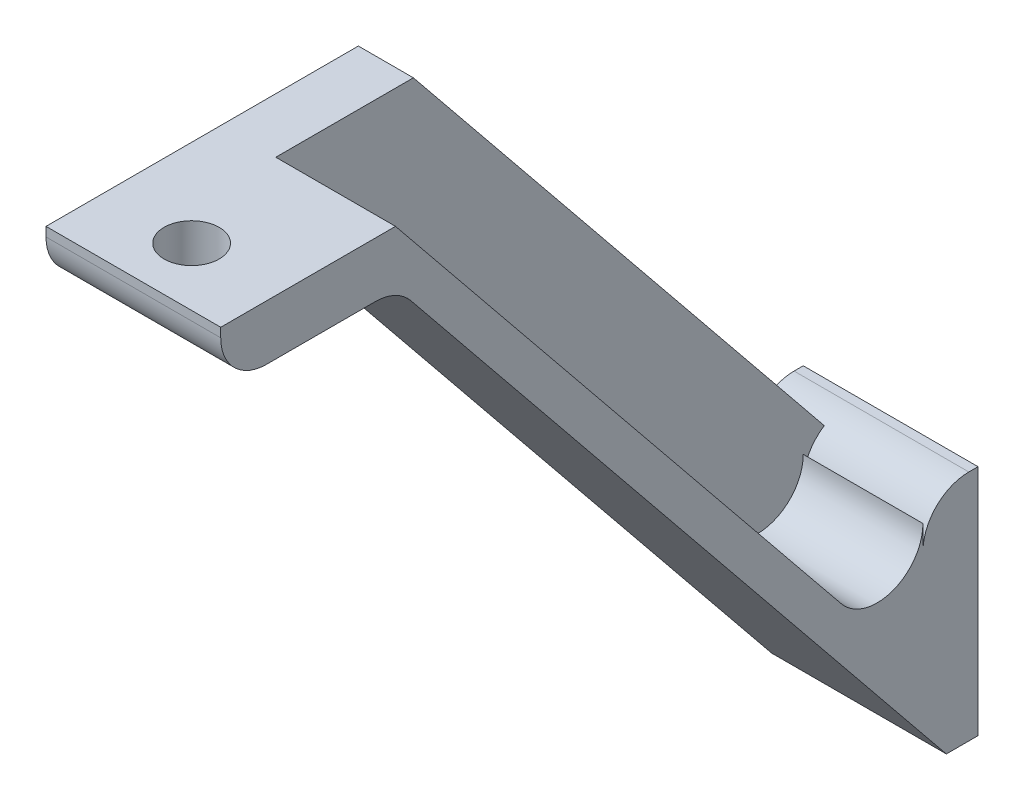
SolidWorks part; units mm, degrees
ref_plane "Front Plane" through (0, 0, 0) normal (0, 0, 1) x (1, 0, 0)
ref_plane "Top Plane" through (0, 0, 0) normal (0, 1, 0) x (1, 0, 0)
ref_plane "Right Plane" through (0, 0, 0) normal (1, 0, 0) x (0, 0, -1)
sketch "Sketch1" plane through (0, 0, 0) normal (1, 0, 0) x (0, 0, -1)
  line L0 (-17.31, 31.3863) -> (31.3064, -28.5635)
  line L1 (-36.36, 31.3863) -> (-17.31, 31.3863)
  line L2 (-36.36, 31.3863) -> (-36.36, 30.3863)
  line L3 (42.7403, -48.4513) -> (46.19, -48.4513)
  line L4 (46.19, -23.0513) -> (46.19, -48.4513)
  line L5 (-36.36, 31.3863) -> (-17.31, 31.3863)
  line L6 (-36.36, 31.3863) -> (-36.36, 25.3863)
  line L7 (-31.36, 25.3863) -> (-19.5212, 25.3863)
  line L9 (46.19, -48.4513) -> (42.7403, -48.4513)
  line L10 (46.19, -48.4513) -> (46.19, -23.0513)
  line L11 (46.19, -23.0513) -> (45.19, -23.0513)
  line L12 (40.19, -25.4142) -> (40.19, -28.0513)
  line L13 (42.7403, -48.4513) -> (-15.6376, 23.5357)
  arc A0 (45.19, -23.0513) -> (40.19, -28.0513) centre (45.19, -28.0513) ccw
  arc A1 (-36.36, 30.3863) -> (-31.36, 25.3863) centre (-31.36, 30.3863) ccw
  arc A2 (31.3064, -28.5635) -> (40.19, -25.4142) centre (35.19, -25.4142) ccw
  arc A3 (-19.5212, 25.3863) -> (-15.6376, 23.5357) centre (-19.5212, 20.3863) cw
  dimension "D1" = 5
  dimension "D2" = 63.5
  dimension "D3" = 180
  dimension "D4" = 25.4
  dimension "D5" = 6
  dimension "D6" = 6
extrude "Boss-Extrude2" add sketch "Sketch1" along normal blind 19.05 contours L7 A3 L13 L3 L4 L11 A0 L12 A2 L0 L1 L2 A1 region at (0, -8.9989, -13.7759)
sketch "Sketch3" plane through (0, 31.3863, 0) normal (0, 1, 0) x (1, 0, 0)
  line L0 (19.05, 46.19) -> (0, 46.19) construction
  circle A0 centre (9.525, -30.01) radius 3
  dimension "D1" = 76.2
  dimension "D2" = 6
extrude "Cut-Extrude1" cut sketch "Sketch3" against normal blind 19.05
sketch "Sketch4" plane through (0, 3.9836, -4.9123) normal (0, 0.6299, -0.7767) x (-1, 0, 0)
  line L1 (0, 35.2809) -> (-6, 35.2809)
  line L2 (0, 35.2809) -> (0, -53.1067)
  line L3 (0, -53.1067) -> (-6, -53.1067)
  line L4 (-6, 35.2809) -> (-6, -53.1067)
  dimension "D1" = 6
extrude "Boss-Extrude3" add sketch "Sketch4" along direction (0, 0, -1) on the side of the normal blind 15
sketch "Sketch5" plane through (19.05, 0, 0) normal (1, 0, 0) x (0, 0, -1)
  line L0 (46.19, -23.0513) -> (46.19, -48.4513) construction
  line L1 (46.19, -25.9204) -> (57.4552, -25.9204)
  line L2 (46.19, -25.9204) -> (46.19, -39.5883)
  line L3 (46.19, -39.5883) -> (57.4552, -39.5883)
  line L4 (57.4552, -25.9204) -> (57.4552, -39.5883)
extrude "Cut-Extrude2" cut sketch "Sketch5" against normal blind 25
fillet "Fillet1" radius 3 rebuild error yes
